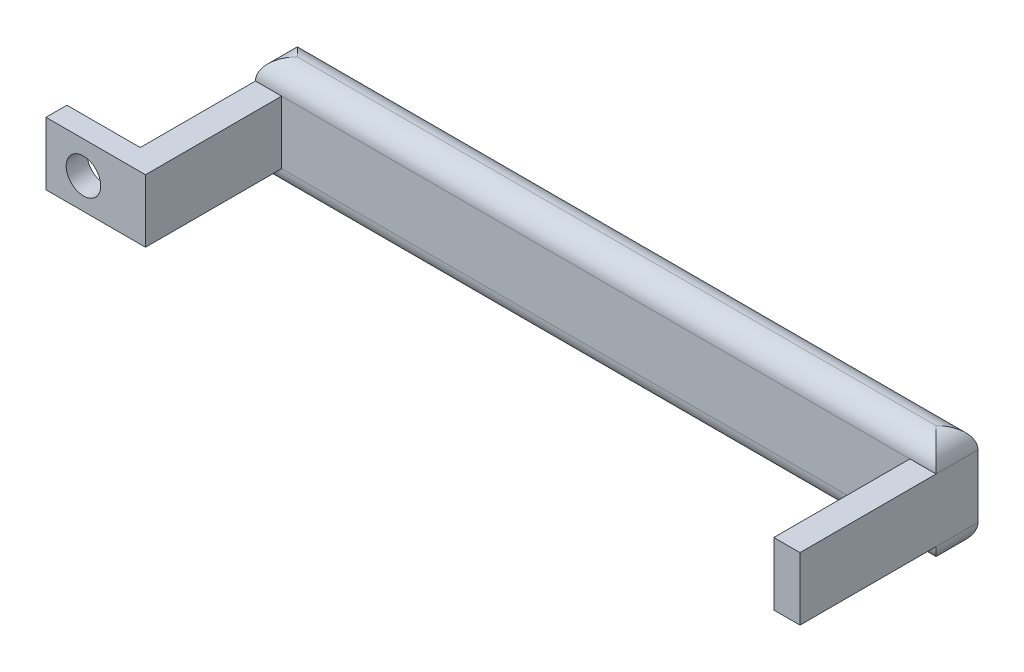
SolidWorks part; units mm, degrees
ref_plane "Plan de face" through (0, 0, 0) normal (0, 0, 1) x (1, 0, 0)
ref_plane "Plan de dessus" through (0, 0, 0) normal (0, 1, 0) x (1, 0, 0)
ref_plane "Plan de droite" through (0, 0, 0) normal (1, 0, 0) x (0, 0, -1)
sketch "Esquisse1" plane through (0, 0, 0) normal (0, 0, 1) x (1, 0, 0)
  line L1 (-38.059, 12.1584) -> (26.941, 12.1584)
  line L2 (-38.059, 12.1584) -> (-38.059, 2.1584)
  line L3 (-38.059, 2.1584) -> (26.941, 2.1584)
  line L4 (26.941, 12.1584) -> (26.941, 2.1584)
  dimension "D1" = 65
  dimension "D2" = 10
extrude "Boss.-Extru.1" add sketch "Esquisse1" along normal blind 4
fillet "Congé1" radius 2 8 edges at (26.941, 12.1584, 2) (-5.559, 12.1584, 4) (-38.059, 12.1584, 2) (-5.559, 12.1584, 0) (-38.059, 2.1584, 2) (-5.559, 2.1584, 4) (26.941, 2.1584, 2) (-5.559, 2.1584, 0)
sketch "Esquisse3" plane through (0, 0, 4) normal (0, 0, 1) x (1, 0, 0)
  line L0 (-38.059, 4.1584) -> (26.941, 4.1584) construction
  line L1 (-38.059, 10.1584) -> (-35.559, 10.1584)
  line L2 (-38.059, 10.1584) -> (-38.059, 4.1584)
  line L3 (-38.059, 4.1584) -> (-35.559, 4.1584)
  line L4 (-35.559, 10.1584) -> (-35.559, 4.1584)
  line L5 (-5.559, 4.1584) -> (-5.559, 7.1367) construction
  line L6 (26.941, 4.1584) -> (24.441, 4.1584)
  line L7 (24.441, 10.1584) -> (24.441, 4.1584)
  line L8 (26.941, 10.1584) -> (24.441, 10.1584)
  line L9 (26.941, 10.1584) -> (26.941, 4.1584)
  dimension "D1" = 2.5
extrude "Boss.-Extru.2" add sketch "Esquisse3" along normal blind 13
sketch "Esquisse4" plane through (0, 0, 17) normal (0, 0, 1) x (1, 0, 0)
  line L0 (-38.059, 4.1584) -> (-35.559, 4.1584) construction
  line L1 (-38.059, 10.1584) -> (-45.059, 10.1584)
  line L2 (-38.059, 10.1584) -> (-38.059, 4.1584)
  line L3 (-38.059, 4.1584) -> (-45.059, 4.1584)
  line L4 (-45.059, 10.1584) -> (-45.059, 4.1584)
  line L11 (-45.059, 10.1584) -> (-38.059, 4.1584) construction
  circle A0 centre (-41.4826, 7.0929) radius 1.65
  dimension "D2" = 3.3
  dimension "D1" = 7
extrude "Boss.-Extru.3" add sketch "Esquisse4" against normal blind 2
